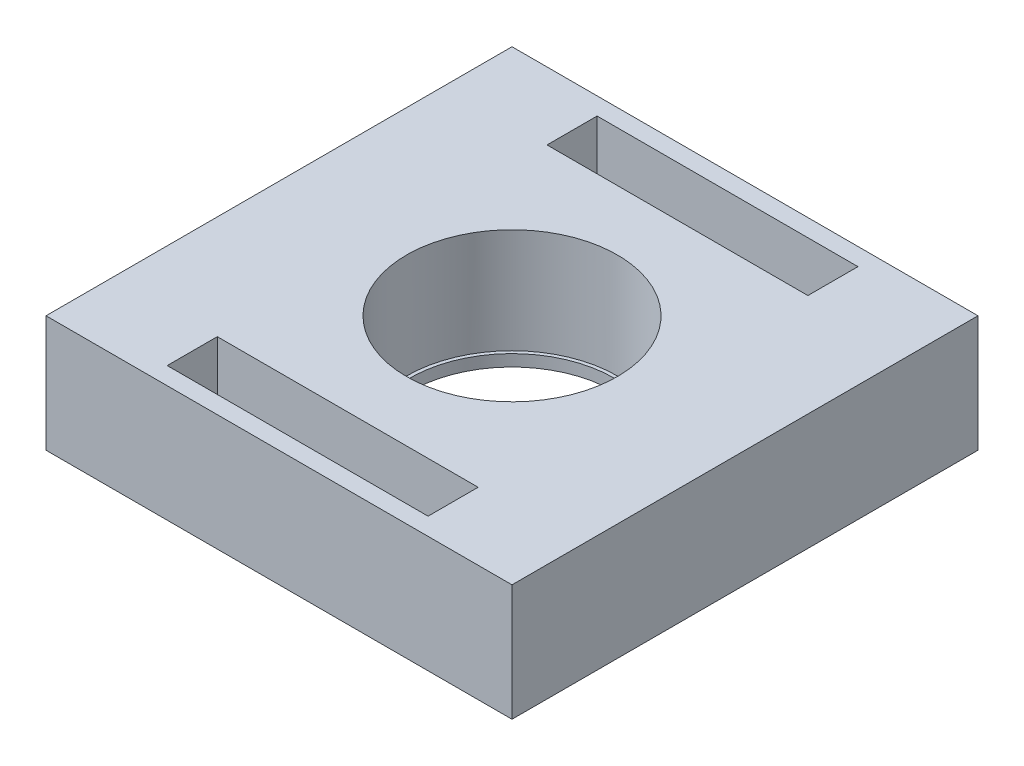
SolidWorks part; units mm, degrees
note: The reader was unsure of these and kept them because the rebuilt part matched: shared geometry of "Sketch3<5>".
material "ABS"
ref_plane "Front Plane" through (0, 0, 0) normal (0, 0, 1) x (1, 0, 0)
ref_plane "Top Plane" through (0, 0, 0) normal (0, 1, 0) x (1, 0, 0)
ref_plane "Right Plane" through (0, 0, 0) normal (1, 0, 0) x (0, 0, -1)
sketch "Sketch1" plane through (0, 0, 0) normal (0, 1, 0) x (1, 0, 0)
  line L1 (-20.0076, -20.0076) -> (20.0076, -20.0076)
  line L2 (-20.0076, -20.0076) -> (-20.0076, 20.0076)
  line L3 (-20.0076, 20.0076) -> (20.0076, 20.0076)
  line L4 (20.0076, -20.0076) -> (20.0076, 20.0076)
  line L5 (-20.0076, -20.0076) -> (20.0076, 20.0076) construction
  line L6 (-20.0076, 20.0076) -> (20.0076, -20.0076) construction
  dimension "D1" = 56.59
extrude "Boss-Extrude1" add sketch "Sketch1" against normal blind 10
sketch "Sketch2" plane through (0, 0, 0) normal (0, 1, 0) x (1, 0, 0)
  circle A0 centre (0, 0) radius 8.75
  dimension "D1" = 17.5
extrude "Cut-Extrude1" cut sketch "Sketch2" against normal through all
sketch "Sketch3" plane through (0, 0, 0) normal (0, 1, 0) x (1, 0, 0)
  line L1 (20.0076, 20.0076) -> (-20.0076, 20.0076) construction
  line L5 (0, 0) -> (0, 14.2076) construction
  line L6 (0, 18.5076) -> (11.2, 18.5076)
  line L7 (-11.1, -14.2076) -> (-11.1, -18.5076)
  line L8 (0, 14.2076) -> (-11.2, 14.2076)
  line L9 (18.5076, -18.5076) -> (18.5076, 18.5076)
  line L10 (18.5076, 18.5076) -> (-18.5076, 18.5076)
  line L11 (-18.5076, 18.5076) -> (-18.5076, -18.5076)
  line L12 (-18.5076, -18.5076) -> (18.5076, -18.5076)
  line L14 (11.2, 18.5076) -> (0, 18.5076)
  line L15 (0, 18.5076) -> (-11.2, 18.5076)
  line L16 (-11.1, -18.5076) -> (11.3, -18.5076)
  line L17 (-11.2, 14.2076) -> (-11.2, 18.5076)
  line L18 (-11.2, 14.2076) -> (11.2, 14.2076)
  line L19 (0, 18.5076) -> (11.2, 18.5076)
  line L21 (0, 14.2076) -> (11.2, 14.2076)
  line L22 (11.2, 18.5076) -> (11.2, 14.2076)
  line L24 (-11.1, -18.5076) -> (11.3, -18.5076)
  line L26 (-11.1, -18.5076) -> (11.3, -18.5076)
  line L27 (-11.1, -18.5076) -> (-11.1, -14.2076)
  line L28 (-11.1, -14.2076) -> (11.3, -14.2076)
  line L29 (11.3, -18.5076) -> (11.3, -14.2076)
  line L30 (11.3, -14.2076) -> (11.3, -18.5076)
  circle A0 centre (0, 0) radius 9.05
  dimension "D2" = 18.1
  dimension "D3" = 11.2
  dimension "D4" = 11.2
  dimension "D5" = 4.3
  dimension "D6" = 4.3
  dimension "D7" = 22.4
  dimension "D1" = 1.5
extrude "Cut-Extrude3" cut sketch "Sketch3" against normal blind 6.7 contours L22 L6 L15 L17 L8 L18 | L16 L29 L28 L7
extrude "Cut-Extrude4" cut sketch "Sketch3<5>" against normal offset from surface (9 mm away) 1 up to face at (0, -10, 8.75)
sketch "Sketch3<5>" plane through (0, 0, 0) normal (0, 1, 0) x (1, 0, 0) same geometry as "Sketch3"
equation "\"1`\"=6"
